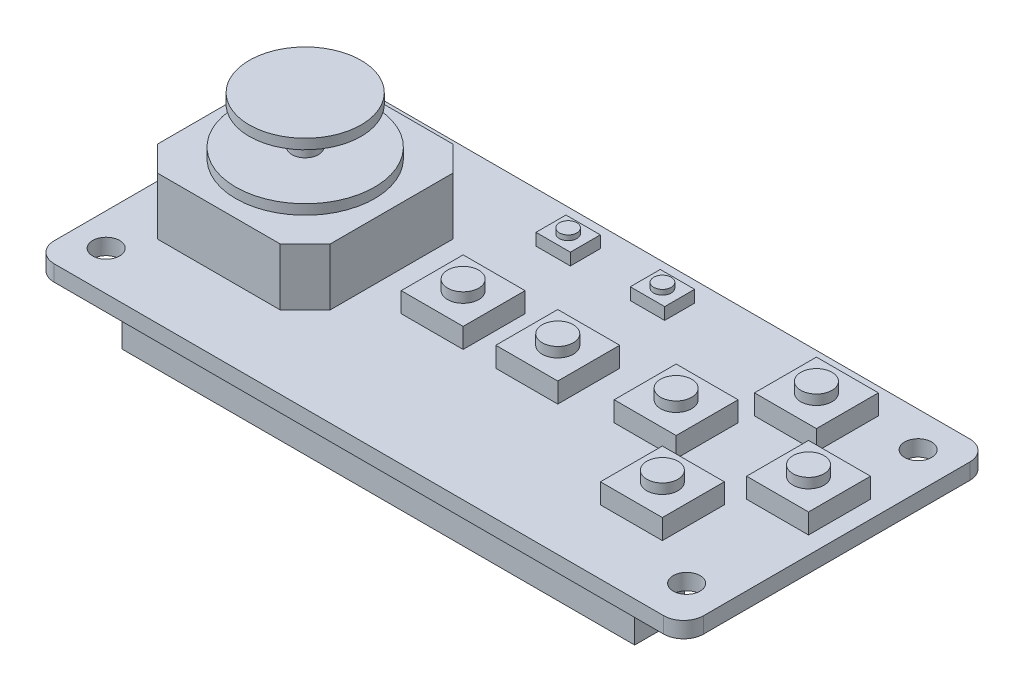
SolidWorks part; units mm, degrees
ref_plane "前视基准面" through (0, 0, 0) normal (0, 0, 1) x (1, 0, 0)
ref_plane "上视基准面" through (0, 0, 0) normal (0, 1, 0) x (1, 0, 0)
ref_plane "右视基准面" through (0, 0, 0) normal (1, 0, 0) x (0, 0, -1)
sketch "草图1" plane through (0, 0, 0) normal (0, 1, 0) x (1, 0, 0)
  line L1 (-35.2962, 18.0875) -> (29.7038, 18.0875)
  line L2 (-35.2962, 18.0875) -> (-35.2962, -12.5525)
  line L3 (-35.2962, -12.5525) -> (29.7038, -12.5525)
  line L4 (29.7038, 18.0875) -> (29.7038, -12.5525)
  dimension "D1" = 65
  dimension "D2" = 30.64
extrude "凸台-拉伸1" add sketch "草图1" along normal blind 1.6
fillet "圆角1" radius 2 4 edges at (-35.2962, 0.8, -18.0875) (-35.2962, 0.8, 12.5525) (29.7038, 0.8, -18.0875) (29.7038, 0.8, 12.5525)
sketch "草图2" plane through (0, 1.6, 0) normal (0, 1, 0) x (1, 0, 0)
  line L0 (-33.2962, -12.5525) -> (27.7038, -12.5525) construction
  line L1 (-35.2962, 16.0875) -> (-35.2962, -10.5525) construction
  line L2 (29.7038, -10.5525) -> (29.7038, 16.0875) construction
  line L3 (27.7038, 18.0875) -> (-33.2962, 18.0875) construction
  circle A0 centre (-32.0462, 14.5675) radius 1.35
  circle A1 centre (26.0538, 14.5675) radius 1.35
  circle A2 centre (26.0538, -8.6025) radius 1.35
  circle A3 centre (-32.0462, -8.6025) radius 1.35
  dimension "D1" = 2.7
  dimension "D2" = 3.95
  dimension "D3" = 3.25
  dimension "D4" = 3.65
  dimension "D5" = 3.52
extrude "切除-拉伸1" cut sketch "草图2" against normal blind 1.6
sketch "草图3" plane through (0, 0, 0) normal (0, -1, 0) x (1, 0, 0)
  line L0 (29.7038, 10.5525) -> (29.7038, -16.0875) construction
  line L1 (23.2038, 5.9525) -> (-28.0962, 5.9525)
  line L2 (23.2038, 5.9525) -> (23.2038, 10.9525)
  line L3 (23.2038, 10.9525) -> (-28.0962, 10.9525)
  line L4 (-28.0962, 5.9525) -> (-28.0962, 10.9525)
  line L5 (-33.2962, 12.5525) -> (27.7038, 12.5525) construction
  dimension "D1" = 51.3
  dimension "D2" = 5
  dimension "D3" = 6.5
  dimension "D4" = 1.6
extrude "凸台-拉伸2" add sketch "草图3" along normal blind 4
sketch "草图4" plane through (0, 1.6, 0) normal (0, 1, 0) x (1, 0, 0)
  line L0 (-35.2962, 16.0875) -> (-35.2962, -10.5525) construction
  line L1 (-32.7862, 12.0575) -> (-15.4862, 12.0575)
  line L2 (-32.7862, 12.0575) -> (-32.7862, -5.2425)
  line L3 (-32.7862, -5.2425) -> (-15.4862, -5.2425)
  line L4 (-15.4862, 12.0575) -> (-15.4862, -5.2425)
  line L5 (27.7038, 18.0875) -> (-33.2962, 18.0875) construction
  dimension "D1" = 17.3
  dimension "D2" = 17.3
  dimension "D3" = 2.51
  dimension "D4" = 6.03
extrude "凸台-拉伸3" add sketch "草图4" along normal blind 5.72
chamfer "倒角1" distance 2.5 angle 45 4 edges at (-15.4862, 4.46, -12.0575) (-32.7862, 4.46, -12.0575) (-32.7862, 4.46, 5.2425) (-15.4862, 4.46, 5.2425)
sketch "草图5" plane through (0, 7.32, 0) normal (0, 1, 0) x (1, 0, 0)
  line L0 (-17.9862, 12.0575) -> (-30.2862, 12.0575) construction
  line L1 (-32.7862, 9.5575) -> (-32.7862, -2.7425) construction
  circle A0 centre (-24.1362, 3.4075) radius 6.95
  point P6 (-24.1362, 12.0575)
  point P10 (-32.7862, 3.4075)
  dimension "D1" = 13.9
extrude "凸台-拉伸4" add sketch "草图5" along normal blind 1
sketch "草图6" plane through (0, 8.32, 0) normal (0, 1, 0) x (1, 0, 0)
  circle A0 centre (-24.1362, 3.4075) radius 1.3261
extrude "凸台-拉伸5" add sketch "草图6" along normal blind 3.72
sketch "草图7" plane through (0, 12.04, 0) normal (0, 1, 0) x (1, 0, 0)
  circle A0 centre (-24.1362, 3.4075) radius 5.6
  dimension "D1" = 11.2
extrude "凸台-拉伸6" add sketch "草图7" along normal blind 1
sketch "草图8" plane through (0, 1.6, 0) normal (0, 1, 0) x (1, 0, 0)
  line L0 (27.7038, 18.0875) -> (-33.2962, 18.0875) construction
  line L1 (-11.6062, 6.6875) -> (-5.4062, 6.6875)
  line L2 (-11.6062, 6.6875) -> (-11.6062, 0.4875)
  line L3 (-11.6062, 0.4875) -> (-5.4062, 0.4875)
  line L4 (-5.4062, 6.6875) -> (-5.4062, 0.4875)
  line L5 (-11.6062, 6.6875) -> (-5.4062, 0.4875) construction
  line L6 (-11.6062, 0.4875) -> (-5.4062, 6.6875) construction
  line L7 (-2.1362, 6.6875) -> (4.0638, 6.6875)
  line L8 (-2.1362, 6.6875) -> (-2.1362, 0.4875)
  line L9 (-2.1362, 0.4875) -> (4.0638, 0.4875)
  line L10 (4.0638, 6.6875) -> (4.0638, 0.4875)
  line L11 (-2.1362, 6.6875) -> (4.0638, 0.4875) construction
  line L12 (-2.1362, 0.4875) -> (4.0638, 6.6875) construction
  line L13 (8.5138, 7.8875) -> (14.7138, 7.8875)
  line L14 (8.5138, 7.8875) -> (8.5138, 1.6875)
  line L15 (8.5138, 1.6875) -> (14.7138, 1.6875)
  line L16 (14.7138, 7.8875) -> (14.7138, 1.6875)
  line L17 (8.5138, 7.8875) -> (14.7138, 1.6875) construction
  line L18 (8.5138, 1.6875) -> (14.7138, 7.8875) construction
  line L19 (14.9338, 15.5075) -> (21.1338, 15.5075)
  line L20 (14.9338, 15.5075) -> (14.9338, 9.3075)
  line L21 (14.9338, 9.3075) -> (21.1338, 9.3075)
  line L22 (21.1338, 15.5075) -> (21.1338, 9.3075)
  line L23 (14.9338, 15.5075) -> (21.1338, 9.3075) construction
  line L24 (14.9338, 9.3075) -> (21.1338, 15.5075) construction
  line L25 (21.7638, 7.8875) -> (27.9638, 7.8875)
  line L26 (21.7638, 7.8875) -> (21.7638, 1.6875)
  line L27 (21.7638, 1.6875) -> (27.9638, 1.6875)
  line L28 (27.9638, 7.8875) -> (27.9638, 1.6875)
  line L29 (21.7638, 7.8875) -> (27.9638, 1.6875) construction
  line L30 (21.7638, 1.6875) -> (27.9638, 7.8875) construction
  line L31 (14.9338, 0.0875) -> (21.1338, 0.0875)
  line L32 (14.9338, 0.0875) -> (14.9338, -6.1125)
  line L33 (14.9338, -6.1125) -> (21.1338, -6.1125)
  line L34 (21.1338, 0.0875) -> (21.1338, -6.1125)
  line L35 (14.9338, 0.0875) -> (21.1338, -6.1125) construction
  line L36 (14.9338, -6.1125) -> (21.1338, 0.0875) construction
  line L37 (-15.4862, -2.7425) -> (-15.4862, 9.5575) construction
  line L38 (29.7038, -10.5525) -> (29.7038, 16.0875) construction
  line L39 (-33.2962, -12.5525) -> (27.7038, -12.5525) construction
  point P0 (-8.5062, 3.5875)
  point P5 (0.9638, 3.5875)
  point P10 (11.6138, 4.7875)
  point P15 (18.0338, 12.4075)
  point P20 (24.8638, 4.7875)
  point P25 (18.0338, -3.0125)
  dimension "D1" = 6.2
  dimension "D2" = 11.4
  dimension "D3" = 3.88
  dimension "D4" = 3.27
  dimension "D5" = 4.45
  dimension "D6" = 10.2
  dimension "D7" = 1.74
  dimension "D8" = 8.57
  dimension "D9" = 6.44
  dimension "D10" = 2.58
extrude "凸台-拉伸7" add sketch "草图8" along normal blind 2
sketch "草图9" plane through (0, 3.6, 0) normal (0, 1, 0) x (1, 0, 0)
  line L0 (-5.4062, 6.6875) -> (-11.6062, 6.6875) construction
  line L1 (-11.6062, 6.6875) -> (-11.6062, 0.4875) construction
  line L2 (4.0638, 6.6875) -> (-2.1362, 6.6875) construction
  line L3 (-2.1362, 6.6875) -> (-2.1362, 0.4875) construction
  line L4 (8.5138, 7.8875) -> (8.5138, 1.6875) construction
  line L5 (14.7138, 7.8875) -> (8.5138, 7.8875) construction
  line L6 (21.1338, 15.5075) -> (14.9338, 15.5075) construction
  line L7 (14.9338, 15.5075) -> (14.9338, 9.3075) construction
  line L8 (27.9638, 7.8875) -> (21.7638, 7.8875) construction
  line L9 (27.9638, 1.6875) -> (27.9638, 7.8875) construction
  line L10 (21.1338, 0.0875) -> (14.9338, 0.0875) construction
  line L11 (21.1338, -6.1125) -> (21.1338, 0.0875) construction
  circle A0 centre (-8.5062, 3.5875) radius 1.56
  circle A1 centre (0.9638, 3.5875) radius 1.56
  circle A2 centre (11.6138, 4.7875) radius 1.56
  circle A3 centre (18.0338, 12.4075) radius 1.56
  circle A4 centre (24.8638, 4.7875) radius 1.56
  circle A5 centre (18.0338, -3.0125) radius 1.56
  point P5 (-8.5062, 6.6875)
  point P9 (-11.6062, 3.5875)
  point P21 (0.9638, 6.6875)
  point P25 (-2.1362, 3.5875)
  point P29 (8.5138, 4.7875)
  point P33 (11.6138, 7.8875)
  point P37 (18.0338, 15.5075)
  point P41 (14.9338, 12.4075)
  point P45 (24.8638, 7.8875)
  point P49 (27.9638, 4.7875)
  point P53 (18.0338, 0.0875)
  point P57 (21.1338, -3.0125)
  dimension "D1" = 3.12
extrude "凸台-拉伸8" add sketch "草图9" along normal blind 1
sketch "草图10" plane through (0, 1.6, 0) normal (0, 1, 0) x (1, 0, 0)
  line L0 (-35.2962, 16.0875) -> (-35.2962, -10.5525) construction
  line L1 (-10.7162, 16.0875) -> (-7.2762, 16.0875)
  line L2 (-10.7162, 16.0875) -> (-10.7162, 13.0875)
  line L3 (-10.7162, 13.0875) -> (-7.2762, 13.0875)
  line L4 (-7.2762, 16.0875) -> (-7.2762, 13.0875)
  line L5 (-10.7162, 16.0875) -> (-7.2762, 13.0875) construction
  line L6 (-10.7162, 13.0875) -> (-7.2762, 16.0875) construction
  line L7 (-1.2762, 16.0875) -> (2.1638, 16.0875)
  line L8 (-1.2762, 16.0875) -> (-1.2762, 13.0875)
  line L9 (-1.2762, 13.0875) -> (2.1638, 13.0875)
  line L10 (2.1638, 16.0875) -> (2.1638, 13.0875)
  line L11 (-1.2762, 16.0875) -> (2.1638, 13.0875) construction
  line L12 (-1.2762, 13.0875) -> (2.1638, 16.0875) construction
  line L13 (27.7038, 18.0875) -> (-33.2962, 18.0875) construction
  point P0 (-8.9962, 14.5875)
  point P5 (0.4438, 14.5875)
  dimension "D1" = 3.44
  dimension "D2" = 3
  dimension "D3" = 3.44
  dimension "D4" = 3
  dimension "D5" = 24.58
  dimension "D6" = 6
  dimension "D7" = 2
extrude "凸台-拉伸9" add sketch "草图10" along normal blind 1.2
sketch "草图11" plane through (0, 2.8, 0) normal (0, 1, 0) x (1, 0, 0)
  line L0 (-7.2762, 16.0875) -> (-10.7162, 16.0875) construction
  line L1 (2.1638, 16.0875) -> (-1.2762, 16.0875) construction
  line L2 (-10.7162, 16.0875) -> (-10.7162, 13.0875) construction
  circle A0 centre (-8.9962, 14.5875) radius 0.875
  circle A1 centre (0.4438, 14.5875) radius 0.875
  point P7 (-8.9962, 16.0875)
  point P11 (0.4438, 16.0875)
  point P15 (-10.7162, 14.5875)
  dimension "D1" = 1.75
extrude "凸台-拉伸10" add sketch "草图11" along normal blind 0.5
